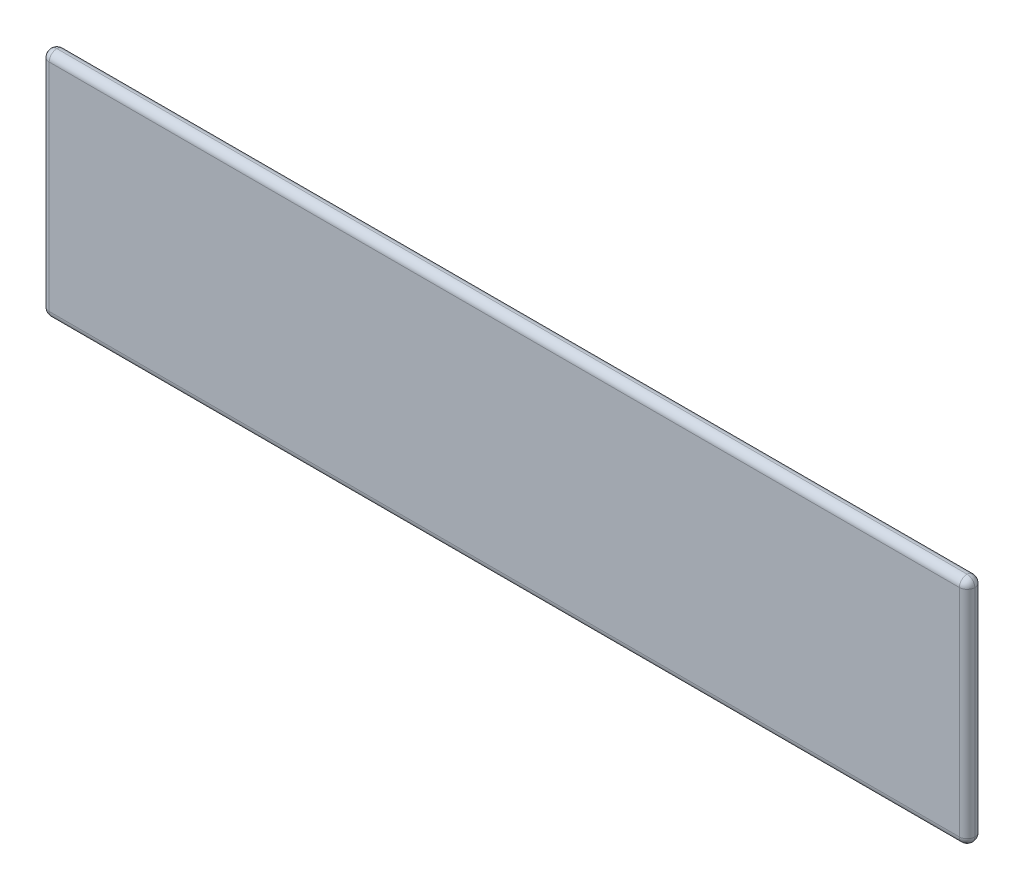
SolidWorks part; units mm, degrees
ref_plane "Front Plane" through (0, 0, 0) normal (0, 0, 1) x (1, 0, 0)
ref_plane "Top Plane" through (0, 0, 0) normal (0, 1, 0) x (1, 0, 0)
ref_plane "Right Plane" through (0, 0, 0) normal (1, 0, 0) x (0, 0, -1)
sketch "Sketch1" plane through (0, 0, 0) normal (0, 0, 1) x (1, 0, 0)
  line L1 (0, 0) -> (1200, 0)
  line L2 (0, 0) -> (0, -300)
  line L3 (0, -300) -> (1200, -300)
  line L4 (1200, 0) -> (1200, -300)
  dimension "D1" = 1200
  dimension "D2" = 300
extrude "Boss-Extrude1" add sketch "Sketch1" along normal mid plane 20
fillet "Fillet1" radius 10 8 edges at (0, -150, -10) (600, -300, -10) (1200, -150, -10) (600, 0, -10) (0, -150, 10) (600, -300, 10) (1200, -150, 10) (600, 0, 10)
